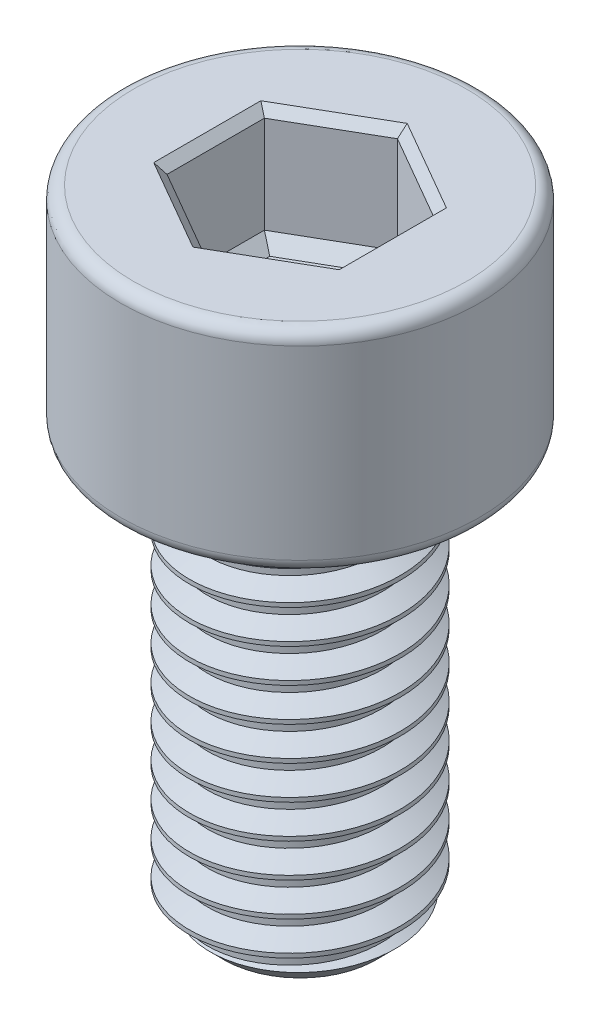
SolidWorks part; units mm, degrees
material "AISI Type A2 Tool Steel"
ref_plane "Front Plane" through (0, 0, 0) normal (0, 0, 1) x (1, 0, 0)
ref_plane "Top Plane" through (0, 0, 0) normal (0, 1, 0) x (1, 0, 0)
ref_plane "Right Plane" through (0, 0, 0) normal (1, 0, 0) x (0, 0, -1)
sketch "Sketch1" plane through (0, 0, 0) normal (0, 1, 0) x (1, 0, 0)
  circle A0 centre (0, 0) radius 2.5
  dimension "D1" = 5
extrude "Boss-Extrude1" add sketch "Sketch1" along normal blind 10
thread "Thread1" pitch 0.8 method cut profile "Thread Profile1" start angle 0, offset 1, length 0, pitch 0.8, diameter 5
ref_plane "Plane1" through (-2.5, 11, 0) normal (0, 0, 1) x (-1, 0, 0)
sketch "Thread Profile1" plane through (-2.5, 11, 0) normal (0, 0, 1) x (-1, 0, 0)
  line L0 (0, 0) -> (0, 0.8) construction
  line L11 (0, 0) -> (0, 0.7)
  line L12 (0, 0.7) -> (-0.433, 0.45)
  line L13 (-0.433, 0.45) -> (-0.433, 0.25)
  line L15 (-0.433, 0.25) -> (0, 0)
  line L17 (-0.433, 0.35) -> (0, 0.35) construction
  point P2 (0, 0)
  dimension "Pitch" = 0.8
  dimension "Profile_Angle" = 60
  dimension "Profile_Land" = 0.2
  dimension "Profile_Height" = 0.433
sketch "Sketch5" plane through (0, 10, 0) normal (0, 1, 0) x (1, 0, 0)
  circle A0 centre (0, 0) radius 4.25
  dimension "D1" = 8.5
extrude "Boss-Extrude2" add sketch "Sketch5" along normal blind 5
fillet "Fillet1" radius 0.3 2 edges at (0, 10, 4.25) (0, 15, 4.25)
sketch "Sketch6" plane through (0, 0, 0) normal (0, 0, 1) x (1, 0, 0)
  line L0 (0, 0) -> (0, 0.2882) construction
  line L1 (0, 0) -> (2.51, 0) construction
  line L2 (2.51, 0) -> (2.51, 0.7)
  line L3 (2.51, 0.7) -> (1.81, 0)
  line L4 (1.81, 0) -> (2.51, 0)
  dimension "D1" = 45
  dimension "D2" = 0.7
  dimension "D3" = 2.51
revolve "Cut-Revolve1" cut sketch "Sketch6" angle 360 about L0
sketch "Sketch7" plane through (0, 15, 0) normal (0, 1, 0) x (1, 0, 0)
  line L1 (0, 2.3094) -> (-2, 1.1547)
  line L2 (-2, 1.1547) -> (-2, -1.1547)
  line L3 (-2, -1.1547) -> (0, -2.3094)
  line L4 (0, -2.3094) -> (2, -1.1547)
  line L5 (2, -1.1547) -> (2, 1.1547)
  line L6 (2, 1.1547) -> (0, 2.3094)
  circle A0 centre (0, 0) radius 2 construction
  dimension "D1" = 4
extrude "Cut-Extrude1" cut sketch "Sketch7" against normal blind 2.5
chamfer "Chamfer1" distance 0.2 angle 45 6 edges at (-2, 15, 0) (-1, 15, 1.7321) (1, 15, 1.7321) (2, 15, 0) (1, 15, -1.7321) (-1, 15, -1.7321)
sketch "Sketch8" plane through (0, 12.5, 0) normal (0, 1, 0) x (1, 0, 0)
  line L1 (0, 2.3094) -> (-2, 1.1547)
  line L2 (-2, 1.1547) -> (-2, -1.1547)
  line L3 (-2, -1.1547) -> (0, -2.3094)
  line L4 (0, -2.3094) -> (2, -1.1547)
  line L5 (2, -1.1547) -> (2, 1.1547)
  line L6 (2, 1.1547) -> (0, 2.3094)
  circle A0 centre (0, 0) radius 2 construction
extrude "Cut-Extrude2" cut sketch "Sketch8" against normal blind 0.3 draft 45
